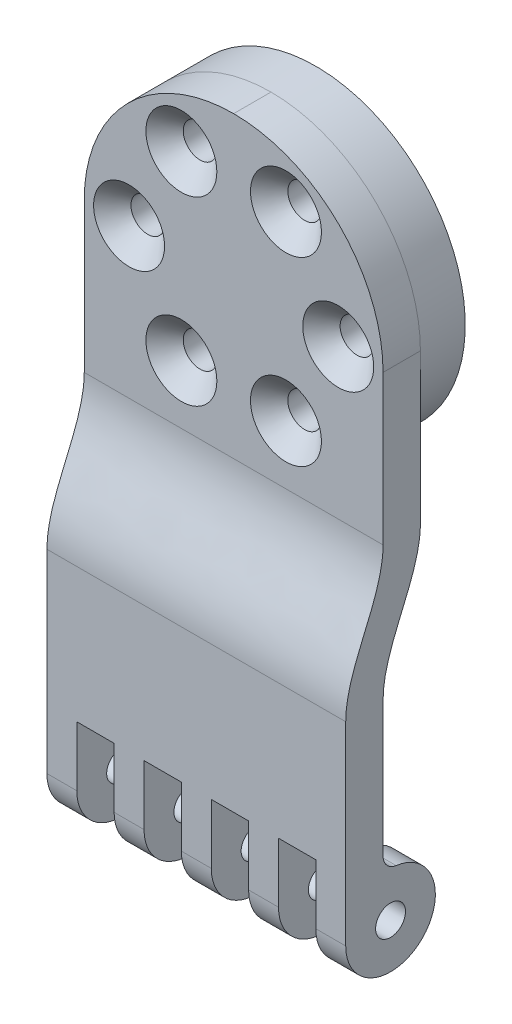
SolidWorks part; units mm, degrees
other "Markup1"
sketch "Sketch13" plane through (20, -53, 11) normal (0.0614, -0.6805, 0.7302) x (0.9699, -0.1321, -0.2046)
ref_plane "Front Plane" through (0, 0, 0) normal (0, 0, 1) x (1, 0, 0)
ref_plane "Top Plane" through (0, 0, 0) normal (0, 1, 0) x (1, 0, 0)
ref_plane "Right Plane" through (0, 0, 0) normal (1, 0, 0) x (0, 0, -1)
sketch "Sketch7" plane through (0, 0, 0) normal (0, 0, 1) x (1, 0, 0)
  line L1 (-20, 20) -> (20, 20)
  line L2 (-20, 20) -> (-20, -20)
  line L3 (-20, -20) -> (20, -20)
  line L4 (20, 20) -> (20, -20)
  line L5 (-20, 20) -> (20, -20) construction
  line L6 (-20, -20) -> (20, 20) construction
  point P0 (0, 0)
extrude "Boss-Extrude1" add sketch "Sketch7" along normal blind 11
ref_plane "Plane2" through (0, -21.4103, 5.7369) normal (0, -0.9659, 0.2588) x (1, 0, 0)
sketch "Sketch8" plane through (0, -20, 2.0782) normal (0, -1, 0) x (1, 0, 0)
  line L0 (20, 8.9218) -> (20, -2.0782) construction
  line L1 (-20, 8.9218) -> (20, 8.9218)
  line L2 (-20, 8.9218) -> (-20, 3.9218)
  line L3 (-20, 3.9218) -> (20, 3.9218)
  line L4 (20, 8.9218) -> (20, 3.9218)
  line L5 (0, 3.9218) -> (0, 8.9218) construction
  line L6 (-20, 6.4218) -> (20, 6.4218) construction
  line L7 (-20, -2.0782) -> (20, -2.0782) construction
  point P764 (0, 6.4218)
  dimension "D1" = 6
ref_plane "Plane4" through (0, -38, 0) normal (0, -1, 0) x (-1, 0, 0)
sketch "Sketch19" plane through (0, -38, 0) normal (0, -1, 0) x (-1, 0, 0)
  line L0 (20, -11) -> (20, 0) construction
  line L1 (20, -16) -> (-20, -16)
  line L2 (20, -16) -> (20, -11)
  line L3 (20, -11) -> (-20, -11)
  line L4 (-20, -16) -> (-20, -11)
  line L5 (20, -16) -> (-20, -11) construction
  line L6 (20, -11) -> (-20, -16) construction
  line L7 (-20, -11) -> (-20, 0) construction
  line L8 (20, -11) -> (-20, -11) construction
  point P4 (0, -13.5)
  dimension "D1" = 5
  dimension "D2" = 5
loft "Loft1" add profiles "Sketch19", "Sketch8" start constraint normal to profile start tangent length 1 end constraint normal to profile end tangent length 1 connector at (-20, -38, 16) connector at (-20, -20, 11)
sketch "Sketch16" plane through (0, 0, 0) normal (0, 0, -1) x (-1, 0, 0)
  line L1 (24.5131, 32.6211) -> (-24.5131, 32.6211)
  line L2 (24.5131, 32.6211) -> (24.5131, -32.6211)
  line L3 (24.5131, -32.6211) -> (-24.5131, -32.6211)
  line L4 (-24.5131, 32.6211) -> (-24.5131, -32.6211)
  line L5 (24.5131, 32.6211) -> (-24.5131, -32.6211) construction
  line L6 (24.5131, -32.6211) -> (-24.5131, 32.6211) construction
  circle A0 centre (0, 0) radius 20
extrude "Cut-Extrude3" cut sketch "Sketch16" against normal blind 6
ref_plane "Plane3" [suppressed] through (0, -56, 0) normal (0, -1, 0) x (-1, 0, 0)
sketch "Sketch17" plane through (0, -38, 0) normal (0, -1, 0) x (-1, 0, 0)
  line L1 (20, -16) -> (-20, -16)
  line L2 (20, -16) -> (20, -11)
  line L3 (20, -11) -> (-20, -11)
  line L4 (-20, -16) -> (-20, -11)
  line L5 (20, -16) -> (-20, -11) construction
  line L6 (20, -11) -> (-20, -16) construction
  line L10 (-20, -16) -> (20, -16) construction
  line L11 (-20, -6) -> (-20, -11) construction
  line L12 (20, -11) -> (20, -6) construction
  point P4 (0, -13.5)
  dimension "D1" = 5
extrude "Boss-Extrude5" add sketch "Sketch17" along normal blind 18
sketch "Sketch10" plane through (0, 0, 11) normal (0, 0, 1) x (1, 0, 0)
  circle A0 centre (-7.0001, 12.1244) radius 2.25
  circle A1 centre (6.9999, 12.1244) radius 2.25
  circle A2 centre (13.9999, 0.0001) radius 2.25
  circle A3 centre (6.9999, -12.1243) radius 2.25
  circle A4 centre (-7.0001, -12.1243) radius 2.25
  circle A5 centre (-14.0001, 0.0001) radius 2.25
  point P0 (0, 0)
  point P1 (0.0025, 0.0011)
  dimension "D4" = 4.5
extrude "Cut-Extrude1" cut sketch "Sketch10" against normal blind 25
sketch "Sketch11" plane through (0, -56, -3.473) normal (0, 1, 0) x (1, 0, 0)
  line L1 (-20, -14.473) -> (-16, -14.473)
  line L2 (-20, -14.473) -> (-20, -19.473)
  line L3 (-20, -19.473) -> (-16, -19.473)
  line L4 (-16, -14.473) -> (-16, -19.473)
  line L5 (-18, -19.473) -> (-18, -14.473) construction
  line L6 (-20, -16.973) -> (-16, -16.973) construction
  line L11 (-20, -14.473) -> (20, -14.473) construction
  line L12 (-20, -14.473) -> (-20, -9.473) construction
  line L13 (20, -19.473) -> (-20, -19.473) construction
  point P368 (-18, -16.973)
  dimension "D1" = 4
extrude "Boss-Extrude3" add sketch "Sketch11" against normal blind 8 contours L1 L4 L3 L2
ref_plane "Plane1" through (-16, 0, 0) normal (1, 0, 0) x (0, 0, -1)
sketch "Sketch14" plane through (-16, 0, 0) normal (1, 0, 0) x (0, 0, -1)
  line L0 (-16, -64) -> (-11, -64) construction
  line L7 (-16, -64) -> (-16, -38) construction
  circle A0 centre (-10, -64) radius 6
  dimension "D3" = 12
  dimension "D1" = 0
extrude "Boss-Extrude4" add sketch "Sketch14" against normal up to vertex (4 mm away) up to point (-20, -20, 11)
pattern_linear "LPattern1" count 5 spacing 9 along (1, 0, 0) of "Boss-Extrude4", "Boss-Extrude3"
sketch "Sketch15" plane through (-20, 0, 0) normal (-1, 0, 0) x (0, 0, 1)
  circle A0 centre (10, -64) radius 2
extrude "Cut-Extrude2" cut sketch "Sketch15" against normal through all
chamfer "Chamfer1" distance 2.5 angle 45 6 edges at (-4.7501, 12.1244, 11) (-11.7501, 0.0001, 11) (-4.7501, -12.1243, 11) (9.2499, 12.1244, 11) (16.2499, 0.0001, 11) (9.2499, -12.1243, 11)
fillet "Fillet2" radius 2 5 edges at (-18, -58.0839, 11) (-9, -58.0839, 11) (0, -58.0839, 11) (9, -58.0839, 11) (18, -58.0839, 11)
fillet "Fillet3" radius 20 2 edges at (20, 20, 8.5) (-20, 20, 8.5)
